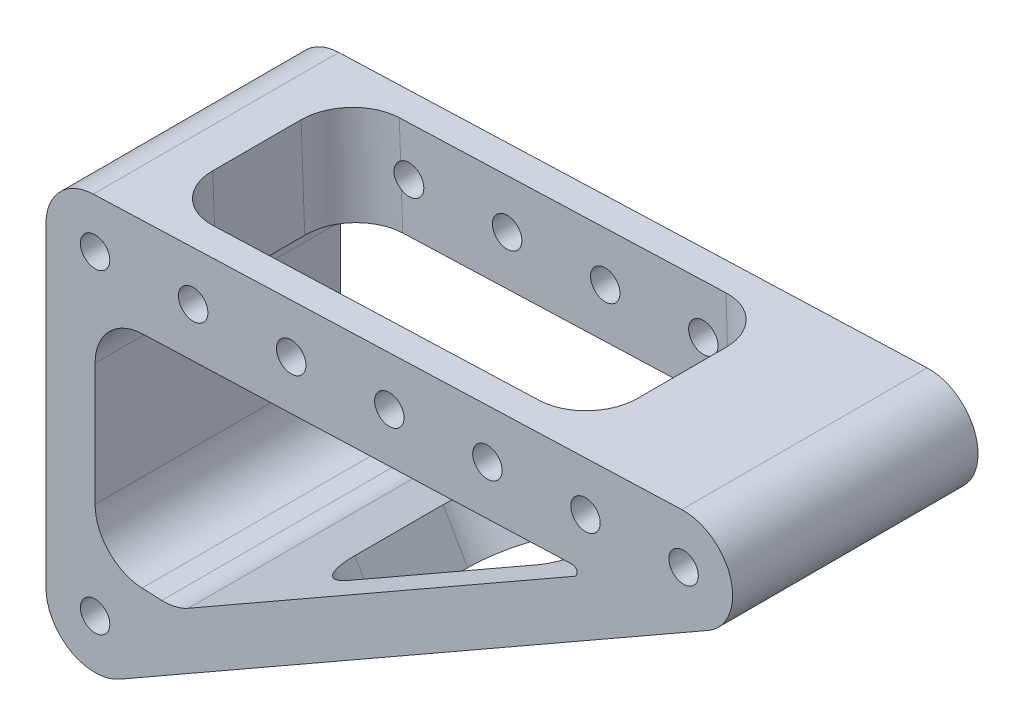
SolidWorks part; units mm, degrees
ref_plane "前视基准面" through (0, 0, 0) normal (0, 0, 1) x (1, 0, 0)
ref_plane "上视基准面" through (0, 0, 0) normal (0, 1, 0) x (1, 0, 0)
ref_plane "右视基准面" through (0, 0, 0) normal (1, 0, 0) x (0, 0, -1)
other "Configuration Table"
sketch "草图1" plane through (0, 0, 0) normal (0, 0, 1) x (1, 0, 0)
  line L0 (89.9427, 18.2122) -> (29.9809, 16.0707)
  line L1 (29.9809, 16.0707) -> (29.9809, -16.0707)
  line L2 (29.9809, -16.0707) -> (89.9427, 18.2122)
  line L3 (110.0211, 23.9325) -> (24.9809, 20.8954)
  line L4 (24.9809, 20.8954) -> (24.9809, -24.689)
  line L5 (24.9809, -24.689) -> (110.0211, 23.9325)
  line L6 (29.9809, 11.0644) -> (80.603, 12.8723)
  line L9 (29.9809, 11.0644) -> (29.9809, -11.0106)
  line L11 (29.9809, -11.0106) -> (38.2224, -11.3587)
  circle A0 centre (89.9427, 18.2122) radius 1.5
  circle A1 centre (79.949, 17.8553) radius 1.5
  circle A2 centre (69.9554, 17.4984) radius 1.5
  circle A3 centre (59.9618, 17.1415) radius 1.5
  circle A4 centre (49.9681, 16.7846) radius 1.5
  circle A5 centre (39.9745, 16.4277) radius 1.5
  circle A6 centre (29.9809, 16.0707) radius 1.5
  circle A7 centre (29.9809, -16.0707) radius 1.5
  dimension "D1" = 5
extrude "凸台-拉伸3" add sketch "草图1" along normal blind 25 contours L4 L5 L3 A7 L1 A6 L0 A5 A4 A3 A2 A1 A0 L2 | A6 L1 L6 L2 A0 L0 A1 A2 A3 A4 A5 | A7 L2 L11 L1 region at (57.659, 14.4857, 0) region at (32.8644, -12.6671, 0) region at (67.0148, 0.4721, 0)
fillet "圆角1" radius 5 1 edges at (110.0211, 23.9325, 12.5) type face fillet first side face at (67.501, 22.4139, 12.5) second side face at (67.501, -0.3783, 12.5)
fillet "圆角2" radius 5 1 edges at (24.9809, 20.8954, 12.5) type face fillet first side face at (57.3725, 22.0522, 12.5) second side face at (24.9809, -1.8968, 12.5)
fillet "圆角3" radius 5 1 edges at (24.9809, -24.689, 12.5) type face fillet first side face at (58.7026, -5.4087, 12.5) second side face at (24.9809, -4.3091, 12.5)
sketch "草图2" plane through (-0.3565, 9.9809, 0) normal (0.0357, -0.9994, 0) x (0.9994, 0.0357, 0)
  line L0 (78.0111, 22) -> (78.0111, 3)
  line L2 (81.0111, 25) -> (81.0111, 0)
  line L3 (81.0111, 0) -> (31.7134, 0)
  line L4 (31.7134, 25) -> (31.7134, 0)
  line L5 (78.0111, 3) -> (34.7134, 3)
  line L6 (34.7134, 22) -> (34.7134, 3)
  line L7 (78.0111, 22) -> (34.7134, 22)
  line L8 (81.0111, 25) -> (31.7134, 25) construction
  dimension "D1" = 3
extrude "切除-拉伸1" cut sketch "草图2" against normal through all contours L0 L7 L6 L5 region at (55.9699, 11.9925, 12.5)
fillet "圆角4" radius 5 1 edges at (77.4264, 17.7636, 22) type face fillet first side face at (77.4264, 17.7636, 12.5) second side face at (71.4554, 17.4984, 22)
fillet "圆角5" radius 5 1 edges at (34.1563, 16.2183, 22) type face fillet first side face at (34.1563, 16.2183, 12.5) second side face at (71.4554, 17.4984, 22)
fillet "圆角6" radius 5 1 edges at (34.1563, 16.2183, 3) type face fillet first side face at (71.4554, 17.4984, 3) second side face at (34.1563, 16.2183, 10)
fillet "圆角7" radius 5 1 edges at (77.4264, 17.7636, 3) type face fillet first side face at (77.4264, 17.7636, 10) second side face at (71.4554, 17.4984, 3)
fillet "圆角8" radius 5 1 edges at (29.9809, 11.0644, 12.5) type face fillet first side face at (55.9699, 11.9925, 12.5) second side face at (29.9809, 0.0269, 12.5)
fillet "圆角9" radius 5 1 edges at (29.9809, -11.0106, 12.5) type face fillet first side face at (29.9809, -2.3854, 12.5) second side face at (34.1016, -11.1847, 12.5)
fillet "圆角10" radius 5 1 edges at (38.2224, -11.3587, 12.5) type face fillet first side face at (36.4961, -11.2858, 12.5) second side face at (59.4127, 0.7568, 12.5)
fillet "圆角11" radius 0.5 1 edges at (80.603, 12.8723, 12.5) type face fillet first side face at (56.7278, 12.0196, 12.5) second side face at (60.0386, 1.1147, 12.5)
sketch "草图4" plane through (14.3109, -25.03, 0) normal (-0.4963, 0.8681, 0) x (0.8681, 0.4963, 0)
  line L0 (71.568, -3) -> (71.568, -22)
  line L2 (74.568, 0) -> (74.568, -25)
  line L3 (74.568, -25) -> (36.329, -25)
  line L4 (36.329, 0) -> (36.329, -25)
  line L5 (71.568, -22) -> (39.329, -22)
  line L6 (39.329, -3) -> (39.329, -22)
  line L7 (71.568, -3) -> (39.329, -3)
  line L8 (74.568, 0) -> (36.329, 0) construction
  dimension "D1" = 3
extrude "切除-拉伸3" cut sketch "草图4" against normal through all contours L0 L7 L6 L5 region at (62.4471, 2.4917, 12.5)
fillet "圆角12" radius 5 1 edges at (77.6817, 8.3223, 22) type face fillet first side face at (63.6879, 0.3214, 22) second side face at (77.6817, 8.3223, 12.5)
fillet "圆角13" radius 5 1 edges at (77.6817, 8.3223, 3) type face fillet first side face at (77.6817, 8.3223, 10) second side face at (63.6879, 0.3214, 3)
fillet "圆角14" radius 5 1 edges at (49.6942, -7.6795, 3) type face fillet first side face at (61.5176, -0.9195, 3) second side face at (49.6942, -7.6795, 12.5)
fillet "圆角15" radius 5 1 edges at (49.6942, -7.6795, 22) type face fillet first side face at (61.5176, -0.9195, 22) second side face at (49.6942, -7.6795, 15)
